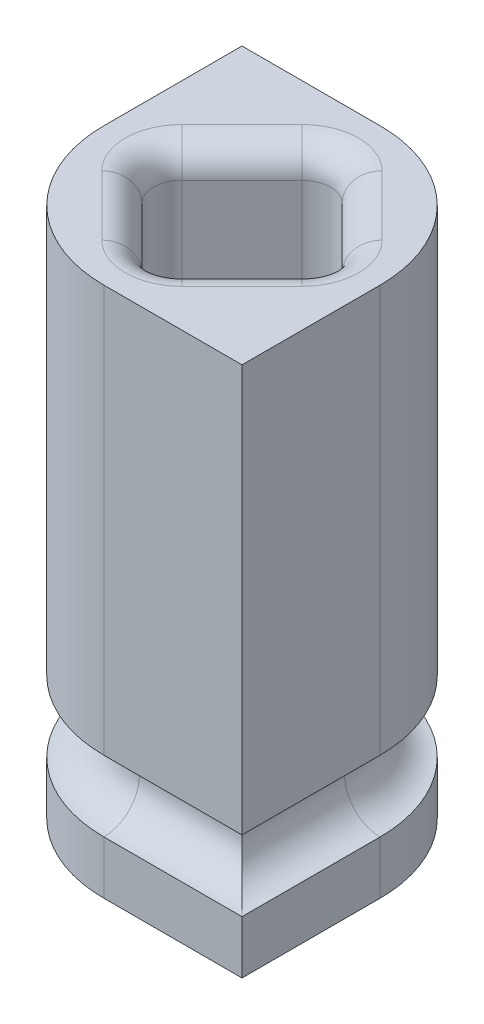
SolidWorks part; units mm, degrees
ref_plane "Front Plane" through (0, 0, 0) normal (0, 0, 1) x (1, 0, 0)
ref_plane "Top Plane" through (0, 0, 0) normal (0, 1, 0) x (1, 0, 0)
ref_plane "Right Plane" through (0, 0, 0) normal (1, 0, 0) x (0, 0, -1)
sketch "Sketch1" plane through (0, 0, 0) normal (0, 1, 0) x (1, 0, 0)
  line L1 (-3.9, 3.9) -> (0, 3.9)
  line L2 (-3.9, 3.9) -> (-3.9, 0)
  line L3 (0, -3.9) -> (3.9, -3.9)
  line L4 (3.9, 0) -> (3.9, -3.9)
  arc A0 (-3.9, 0) -> (0, -3.9) centre (0, 0) ccw
  arc A1 (3.9, 0) -> (0, 3.9) centre (0, 0) ccw
  point P0 (0, 0)
  dimension "D3" = 3.9
  dimension "D4" = 3.9
  dimension "D1" = 7.8
  dimension "D2" = 7.8
  dimension "D5" = 3.9
  dimension "D6" = 3.9
  dimension "D7" = 3.9
  dimension "D8" = 3.9
extrude "Boss-Extrude1" add sketch "Sketch1" along normal blind 5
ref_plane "Plane1" through (0, 2.5, 0) normal (0, 1, 0) x (1, 0, 0)
sketch "Sketch3" plane through (0, 2.5, 0) normal (0, 1, 0) x (1, 0, 0)
  line L0 (-3.9, 0) -> (-3.9, 3.9)
  line L1 (-3.9, 3.9) -> (0, 3.9)
  line L2 (3.9, 0) -> (3.9, -3.9)
  line L3 (3.9, -3.9) -> (0, -3.9)
  line L4 (-2.9, 0) -> (-2.9, 2.9)
  line L5 (-2.9, 2.9) -> (0, 2.9)
  line L6 (2.9, 0) -> (2.9, -2.9)
  line L7 (2.9, -2.9) -> (0, -2.9)
  arc A0 (-3.9, 0) -> (0, -3.9) centre (0, 0) ccw
  arc A1 (3.9, 0) -> (0, 3.9) centre (0, 0) ccw
  arc A2 (2.9, 0) -> (0, 2.9) centre (0, 0) ccw
  arc A3 (-2.9, 0) -> (0, -2.9) centre (0, 0) ccw
  dimension "D1" = 1
extrude "Cut-Extrude2" cut sketch "Sketch3" against normal blind 1 and the other way blind 1
fillet "Fillet1" radius 1 12 edges at (2.9, 3.5, 1.45) (2.0506, 3.5, -2.0506) (1.45, 3.5, 2.9) (-2.0506, 3.5, 2.0506) (2.9, 1.5, 1.45) (2.0506, 1.5, -2.0506) (-2.9, 1.5, -1.45) (1.45, 1.5, 2.9) (-1.45, 3.5, -2.9) (-2.9, 3.5, -1.45) (-1.45, 1.5, -2.9) (-2.0506, 1.5, 2.0506)
sketch "Sketch4" plane through (0, 5, 0) normal (0, 1, 0) x (1, 0, 0)
  line L0 (0, 3.9) -> (-3.9, 3.9)
  line L1 (-3.9, 3.9) -> (-3.9, 0)
  line L2 (3.9, 0) -> (3.9, -3.9)
  line L3 (3.9, -3.9) -> (0, -3.9)
  line L4 (-2.2627, -0.5657) -> (-0.5657, -2.2627)
  line L5 (-2.2627, 0.5657) -> (-0.5657, 2.2627)
  line L6 (0.5657, -2.2627) -> (2.2627, -0.5657)
  line L7 (0.5657, 2.2627) -> (2.2627, 0.5657)
  line L8 (-2.8284, 0) -> (2.8284, 0) construction
  line L9 (0, -2.8284) -> (0, 2.8284) construction
  arc A1 (3.9, 0) -> (0, 3.9) centre (0, 0) ccw
  arc A2 (-3.9, 0) -> (0, -3.9) centre (0, 0) ccw
  arc A3 (-0.5657, -2.2627) -> (0.5657, -2.2627) centre (0, -1.6971) ccw
  arc A4 (2.2627, -0.5657) -> (2.2627, 0.5657) centre (1.6971, 0) ccw
  arc A5 (-0.5657, 2.2627) -> (0.5657, 2.2627) centre (0, 1.6971) cw
  arc A6 (-2.2627, 0.5657) -> (-2.2627, -0.5657) centre (-1.6971, 0) ccw
  dimension "D5" = 0.8
  dimension "D2" = 45
  dimension "D3" = 4
  dimension "D4" = 4
extrude "Boss-Extrude3" add sketch "Sketch4" along normal blind 10
fillet "Fillet2" radius 0.8 8 edges at (0, 15, -2.4971) (1.4142, 15, -1.4142) (2.4971, 15, 0) (1.4142, 15, 1.4142) (0, 15, 2.4971) (-1.4142, 15, 1.4142) (-2.4971, 15, 0) (-1.4142, 15, -1.4142)
